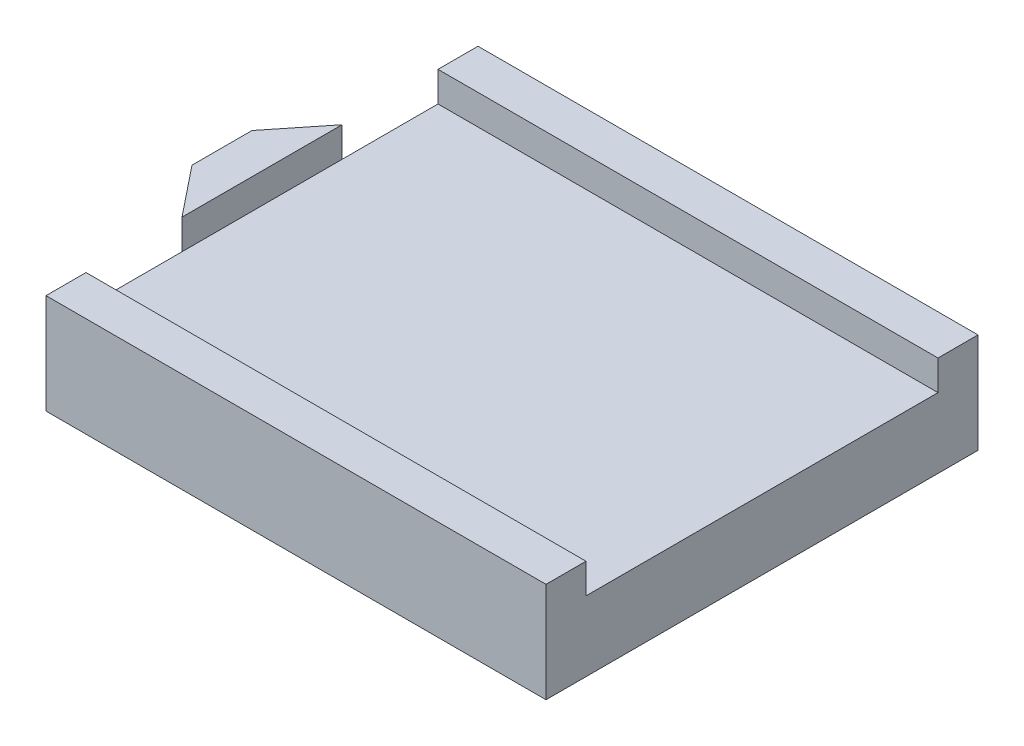
SolidWorks part; units mm, degrees
ref_plane "Plano frontal" through (0, 0, 0) normal (0, 0, 1) x (1, 0, 0)
ref_plane "Plano superior" through (0, 0, 0) normal (0, 1, 0) x (1, 0, 0)
ref_plane "Plano direito" through (0, 0, 0) normal (1, 0, 0) x (0, 0, -1)
sketch "Esboço1" plane through (0, 0, 0) normal (0, 1, 0) x (1, 0, 0)
  line L0 (12.5, 8.8) -> (-12.5, 8.8)
  line L1 (12.5, -10.8) -> (-12.5, -10.8)
  line L2 (12.5, -10.8) -> (12.5, 10.8)
  line L3 (12.5, 10.8) -> (-12.5, 10.8)
  line L4 (-12.5, -10.8) -> (-12.5, 10.8)
  line L5 (12.5, -10.8) -> (-12.5, 10.8) construction
  line L6 (12.5, 10.8) -> (-12.5, -10.8) construction
  line L7 (-12.5, -8.8) -> (12.5, -8.8)
  line L8 (0, 0) -> (-22.8329, 0) construction
  line L9 (-14.5, -1.5) -> (-12.5, -4)
  line L10 (-14.5, -1.5) -> (-12.5, -1.5)
  line L11 (-14.5, -1.5) -> (-14.5, 1.5)
  line L12 (-14.5, 1.5) -> (-12.5, 1.5)
  line L13 (-12.5, -1.5) -> (-12.5, 1.5)
  line L14 (-14.5, -1.5) -> (-12.5, 1.5) construction
  line L15 (-14.5, 1.5) -> (-12.5, -1.5) construction
  line L16 (-14.5, 1.5) -> (-12.5, 4)
  line L17 (-14.5, -1.5) -> (-12.5, -1.5)
  line L18 (-14.5, 1.5) -> (-12.5, 1.5)
  point P0 (0, 0)
  point P14 (-13.5, 0)
  dimension "D1" = 21.6
  dimension "D2" = 25
  dimension "D3" = 2
  dimension "D4" = 2
  dimension "D5" = 2
  dimension "D6" = 3
  dimension "D7" = 4
extrude "Ressalto-extrusão1" add sketch "Esboço1" along normal blind 3.5 contours L4 L7 L2 L0 region at (0, 0, 0)
extrude "Ressalto-extrusão2" add sketch "Esboço1<3>" along normal blind 5 contours L7 L4 L1 L2 | L4 L0 L2 L3 | L16 L12 L4 | L12 L11 L10 L4 | L10 L9 L4 region at (0, 0, -9.8) region at (0, 0, 9.8) region at (-13.1667, 0, -2.3333) region at (-13.5, 0, 0) region at (-13.1667, 0, 2.3333)
sketch "Esboço1<3>" plane through (0, 0, 0) normal (0, 1, 0) x (1, 0, 0) same geometry as "Esboço1"
sketch "Esboço2" plane through (0, 0, 0) normal (0, -1, 0) x (1, 0, 0)
  line L0 (0, 0) -> (0, 10.8) construction
  line L1 (12.5, 10.8) -> (-12.5, 10.8) construction
  line L2 (0, 0) -> (12.5, 0) construction
  line L3 (12.5, 10.8) -> (12.5, -10.8) construction
  circle A0 centre (8.5, 7.8) radius 1.55
  circle A1 centre (-8.5, 7.8) radius 1.55
  circle A2 centre (-8.5, -7.8) radius 1.55
  circle A3 centre (8.5, -7.8) radius 1.55
  dimension "D1" = 3.1
  dimension "D2" = 3
  dimension "D3" = 4
extrude "Corte-extrusão1" cut sketch "Esboço2" against normal blind 2.2
